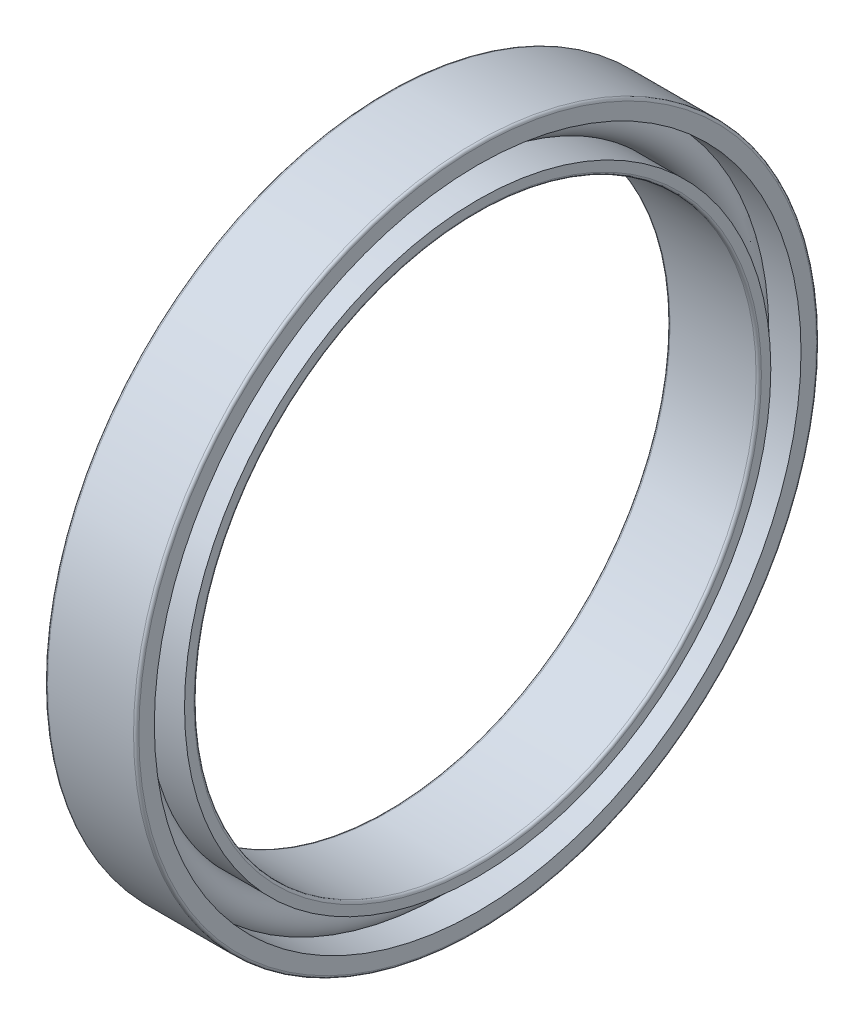
SolidWorks part; units mm, degrees
ref_plane "Plane1" through (0, 0, 0) normal (0, 0, 1) x (1, 0, 0)
ref_plane "Plane2" through (0, 0, 0) normal (0, 1, 0) x (1, 0, 0)
ref_plane "Plane3" through (0, 0, 0) normal (1, 0, 0) x (0, 0, -1)
other "Configuration Table"
sketch "Clipboard" plane through (0, 0, 0) normal (0, 0, 1) x (1, 0, 0)
  line L0 (-10, 0) -> (10, 0) construction
  line L1 (0, 0) -> (22.3471, -0.7804)
  line L2 (0, 0) -> (1106.8253, 38.6512)
  line L3 (0, 0) -> (22.3471, -0.7804)
  line L4 (0, 0) -> (-22.3573, -0.3902)
  dimension "BallCLRad" = 1107.5
sketch "CagSpiSke" plane through (0, 0, 0) normal (0, 0, 1) x (1, 0, 0)
  line L0 (16.125, 1096.75) -> (16.125, 1118.25)
  line L1 (16.125, 1118.25) -> (-16.125, 1118.25)
  line L2 (-16.125, 1118.25) -> (-16.125, 1096.75)
  line L3 (-16.125, 1096.75) -> (16.125, 1096.75)
  line L4 (-20.6375, 0) -> (20.6375, 0) construction
  line L5 (0, 0) -> (0, 23.7692) construction
  dimension "OD" = 2236.5
  dimension "ID" = 2193.5
revolve "CageSpine" add sketch "CagSpiSke" angle 0.001 about L4
ref_axis "Axis1" through (-50, 0, 0) along (1, 0, 0)
sketch "CagBalSke" plane through (0, 0, 0) normal (0, 0, 1) x (1, 0, 0)
  line L0 (-70.95, 1107.5) -> (70.95, 1107.5)
  line L1 (-1.905, 1107.5) -> (1.905, 1107.5) construction
  line L2 (-10, 0) -> (10, 0) construction
  line L3 (0, 0) -> (0, 24) construction
  arc A0 (70.95, 1107.5) -> (-70.95, 1107.5) centre (0, 1107.5) cw
  dimension "BallCLRad" = 1107.5
revolve "CageBall" [suppressed] add sketch "CagBalSke" angle 360 about L1 reverse direction yes
pattern_circular "CageBalls" [suppressed] count 2 every 180 about axis through (-50, 0, 0) along (1, 0, 0)
sketch "CagTrmODSke" plane through (0, 0, 0) normal (0, 0, 1) x (1, 0, 0)
  line L0 (70.951, 1118.25) -> (70.951, 1178.451)
  line L1 (70.951, 1178.451) -> (-70.951, 1178.451)
  line L2 (-70.951, 1178.451) -> (-70.951, 1118.25)
  line L3 (-70.951, 1118.25) -> (70.951, 1118.25)
  line L4 (-20.6375, 0) -> (20.6375, 0) construction
  line L5 (0, 0) -> (0, 25) construction
  dimension "Width" = 141.902
  dimension "ID" = 2236.5
  dimension "OD" = 2356.902
revolve "CageTrimOD" [suppressed] cut sketch "CagTrmODSke" angle 360 about L4 reverse direction yes
sketch "CagTrmIDSke" plane through (0, 0, 0) normal (0, 0, 1) x (1, 0, 0)
  line L0 (70.951, 1036.551) -> (70.951, 1096.75)
  line L1 (70.951, 1096.75) -> (-70.951, 1096.75)
  line L2 (-70.951, 1096.75) -> (-70.951, 1036.551)
  line L3 (-70.951, 1036.551) -> (70.951, 1036.551)
  line L4 (-20.6375, 0) -> (20.6375, 0) construction
  line L5 (0, 0) -> (0, 25) construction
  dimension "Width" = 141.902
  dimension "ID" = 2073.102
  dimension "OD" = 2193.5
revolve "CageTrimID" [suppressed] cut sketch "CagTrmIDSke" angle 360 about L4 reverse direction yes
sketch "BalSimSke" plane through (0, 0, 0) normal (0, 0, 1) x (1, 0, 0)
  line L0 (-10, 0) -> (10, 0) construction
  line L1 (-10, 1107.5) -> (10, 1107.5) construction
  line L2 (0, 0) -> (0, 23) construction
  circle A0 centre (0, 1107.5) radius 64.5
  dimension "BallCLRad" = 1107.5
  dimension "Ball_diameter" = 129
revolve "BallsSimplified" add sketch "BalSimSke" angle 360 about L0
sketch "BalDetSke" plane through (0, 0, 0) normal (0, 0, 1) x (1, 0, 0)
  line L0 (-64.5, 1107.5) -> (64.5, 1107.5)
  line L1 (-1.905, 1107.5) -> (1.905, 1107.5) construction
  line L2 (0, 0) -> (0, 25) construction
  arc A0 (64.5, 1107.5) -> (-64.5, 1107.5) centre (0, 1107.5) cw
  dimension "BallCLRad" = 1107.5
  dimension "Ball_diameter" = 129
revolve "BallDetailed" [suppressed] add sketch "BalDetSke" angle 360 about L1 reverse direction yes
sketch "InnRacSke" plane through (0, 0, 0) normal (0, 0, 1) x (1, 0, 0)
  line L0 (-48.0419, 1064.5) -> (-162.5, 1064.5)
  line L1 (-162.5, 1064.5) -> (-162.5, 1009.5)
  line L2 (-153, 1000) -> (153, 1000)
  line L3 (162.5, 1009.5) -> (162.5, 1043.025)
  line L4 (0, 1043.025) -> (162.5, 1043.025)
  line L5 (-20.6375, 0) -> (20.6375, 0) construction
  line L6 (0, 0) -> (0, 30) construction
  arc A0 (-162.5, 1009.5) -> (-153, 1000) centre (-153, 1009.5) ccw
  arc A1 (153, 1000) -> (162.5, 1009.5) centre (153, 1009.5) ccw
  arc A2 (0, 1043.025) -> (-48.0419, 1064.5) centre (0, 1107.5) cw
  dimension "BallCLRad" = 1107.5
  dimension "Fillet_radius" = 9.5
  dimension "Ball_diameter" = 128.95
  dimension "ID" = 2000
  dimension "OD" = 2129
  dimension "Width" = 325
revolve "InnerRace" add sketch "InnRacSke" angle 360 about L5 reverse direction yes
sketch "OutRacSke" plane through (0, 0, 0) normal (0, 0, 1) x (1, 0, 0)
  line L0 (0, 1171.975) -> (-162.5, 1171.975)
  line L1 (-162.5, 1171.975) -> (-162.5, 1205.5)
  line L2 (-153, 1215) -> (153, 1215)
  line L3 (162.5, 1205.5) -> (162.5, 1150.5)
  line L4 (162.5, 1150.5) -> (48.0419, 1150.5)
  line L5 (-20.6375, 0) -> (20.6375, 0) construction
  line L6 (0, 0) -> (0, 30) construction
  arc A0 (-162.5, 1205.5) -> (-153, 1215) centre (-153, 1205.5) cw
  arc A1 (153, 1215) -> (162.5, 1205.5) centre (153, 1205.5) cw
  arc A2 (48.0419, 1150.5) -> (0, 1171.975) centre (0, 1107.5) ccw
  dimension "BallCLRad" = 1107.5
  dimension "Fillet_radius" = 9.5
  dimension "Ball_diameter" = 128.95
  dimension "Width" = 325
revolve "OuterRace" add sketch "OutRacSke" angle 360 about L5 reverse direction yes
pattern_circular "BallsDetailed" [suppressed] count 2 every 180 about axis through (-50, 0, 0) along (1, 0, 0)
equation "\"BallCLRad@Clipboard\" = ( \"OD@OutRacSke\" + \"ID@InnRacSke\" ) / 4"
equation "\"BallCLRad@BalSimSke\" = \"BallCLRad@Clipboard\""
equation "\"BallCLRad@BalDetSke\" = \"BallCLRad@Clipboard\""
equation "\"BallCLRad@InnRacSke\" = \"BallCLRad@Clipboard\""
equation "\"BallCLRad@OutRacSke\" = \"BallCLRad@Clipboard\""
equation "\"Ball_diameter@InnRacSke\" = \"Ball_diameter@BalDetSke\" - 0.05"
equation "\"Ball_diameter@OutRacSke\" = \"Ball_diameter@BalDetSke\" - 0.05"
equation "\"Ball_diameter@BalSimSke\" = \"Ball_diameter@BalDetSke\""
equation "\"Width@OutRacSke\" = \"Width@InnRacSke\""
equation "\"Fillet_radius@OutRacSke\" = \"Fillet_radius@InnRacSke\""
equation "\"Max_count@Clipboard\" = int( 3.14159265 / atn(( \"Ball_diameter@BalDetSke\" / 2) / sqr( \"BallCLRad@Clipboard\"  *  \"BallCLRad@Clipboard\" - ( \"Ball_diameter@BalDetSke\" / 2) *  ( \"Ball_diameter@BalDetSke\" / 2))))"
equation "\"Max_count@Clipboard\" = ((sgn( \"Max_count@Clipboard\" - \"Count@Clipboard\" )-1)*( \"Max_count@Clipboard\" - \"Count@Clipboard\" ))/-2+ \"Count@Clipboard\""
equation "\"Count@BallsDetailed\" = int( \"Show_count@Clipboard\" ) "
equation "\"Count@BallsDetailed\" = ((sgn( \"Count@BallsDetailed\" - \"Max_count@Clipboard\" )-1)*( \"Count@BallsDetailed\" - \"Max_count@Clipboard\" ))/-2+ \"Max_count@Clipboard\""
equation "\"Count@BallsDetailed\" = ((sgn( \"Count@BallsDetailed\" - \"Min_count@Clipboard\" )+1)*( \"Count@BallsDetailed\" - \"Min_count@Clipboard\"))/2 +\"Min_count@Clipboard\""
equation "\"Angle@BallsDetailed\" = 360.0 / \"Max_count@Clipboard\""
equation "\"BallCLRad@CagBalSke\" = \"BallCLRad@Clipboard\""
equation "\"Count@CageBalls\" = \"Count@BallsDetailed\""
equation "\"Angle@CageBalls\" = \"Angle@BallsDetailed\""
equation "\"Angle@CageSpine\" =  \"Angle@CageBalls\" * ( \"Count@CageBalls\" -1 + int( \"Count@CageBalls\" / \"Max_count@Clipboard\" ) )  + 0.001 -  int( \"Count@CageBalls\" / \"Max_count@Clipboard\" ) * 0.001"
equation "\"Angle@CageSpine\" =  \"Angle@CageSpine\" * int( \"Min_count@Clipboard\" / 2) + int(1 / \"Min_count@Clipboard\")  * 0.001"
equation "\"CageWallOD@CagBalSke\" =  \"Ball_diameter@BalDetSke\" * 1.1"
equation "\"Thickness@CagSpiSke\" =  \"Ball_diameter@BalDetSke\" * 0.25"
equation "\"OD@CagTrmODSke\" = \"BallCLRad@Clipboard\" * 2 + \"CageWallOD@CagBalSke\" + 0.002"
equation "\"ID@CagTrmODSke\" = \"BallCLRad@Clipboard\" * 2 + \"Ball_diameter@BalDetSke\" / 6"
equation "\"OD@CagTrmIDSke\" = \"BallCLRad@Clipboard\" * 2 - \"Ball_diameter@BalDetSke\" / 6"
equation "\"ID@CagTrmIDSke\" = \"BallCLRad@Clipboard\" * 2 - \"CageWallOD@CagBalSke\" + 0.002"
equation "\"OD@CagSpiSke\" = \"ID@CagTrmODSke\""
equation "\"ID@CagSpiSke\" = \"OD@CagTrmIDSke\""
equation "\"Width@CagTrmODSke\" = \"CageWallOD@CagBalSke\" + 0.002"
equation "\"Width@CagTrmIDSke\" = \"CageWallOD@CagBalSke\" + 0.002"
